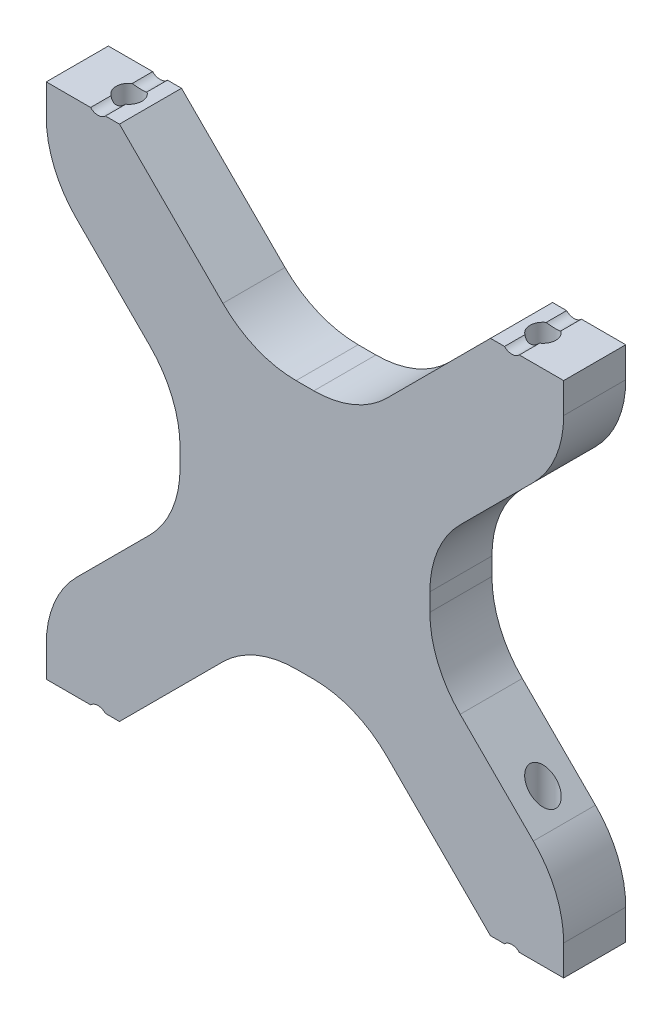
SolidWorks part; units mm, degrees
ref_plane "正面" through (0, 0, 0) normal (0, 0, 1) x (1, 0, 0)
ref_plane "平面" through (0, 0, 0) normal (0, 1, 0) x (1, 0, 0)
ref_plane "右側面" through (0, 0, 0) normal (1, 0, 0) x (0, 0, -1)
sketch "ｽｹｯﾁ1" plane through (0, 0, 0) normal (0, 0, 1) x (1, 0, 0)
  line L0 (-32.0711, 25) -> (-12.0711, 5)
  line L1 (-12.0711, -5) -> (-32.0711, -25)
  line L2 (-32.0711, -25) -> (-17.9289, -25)
  line L3 (-17.9289, -25) -> (-5, -12.0711)
  line L4 (5, -12.0711) -> (17.9289, -25)
  line L5 (17.9289, -25) -> (32.0711, -25)
  line L6 (32.0711, -25) -> (12.0711, -5)
  line L7 (12.0711, 5) -> (32.0711, 25)
  line L8 (32.0711, 25) -> (17.9289, 25)
  line L9 (17.9289, 25) -> (5, 12.0711)
  line L10 (-5, 12.0711) -> (-17.9289, 25)
  line L11 (-17.9289, 25) -> (-32.0711, 25)
  line L12 (-12.0711, 5) -> (-12.0711, -5)
  line L13 (-5, -12.0711) -> (5, -12.0711)
  line L14 (12.0711, -5) -> (12.0711, 5)
  line L15 (5, 12.0711) -> (-5, 12.0711)
  line L16 (12.0711, 5) -> (-12.0711, -5) construction
  line L17 (-12.0711, 5) -> (12.0711, -5) construction
  line L18 (-12.0711, 5) -> (12.0711, 5) construction
  line L19 (5, 12.0711) -> (-5, -12.0711) construction
  line L20 (-5, 12.0711) -> (5, -12.0711) construction
  point P1 (0, 0)
  point P11 (0, 0)
  dimension "D1" = 10
  dimension "D2" = 135
  dimension "D3" = 10
  dimension "D4" = 10
  dimension "D5" = 50
  dimension "D6" = 135
extrude "ﾎﾞｽ - 押し出し1" add sketch "ｽｹｯﾁ1" along normal blind 6
sketch "ｽｹｯﾁ2" plane through (0, 0, 6) normal (0, 0, 1) x (1, 0, 0)
  line L0 (0, 0) -> (0, 38.1314) construction
  line L1 (-17.9289, 25) -> (-32.0711, 25) construction
  line L2 (-20.7141, 25) -> (-19.2859, 25)
  line L3 (20.7141, 25) -> (19.2859, 25)
  arc A0 (-20.7141, 25) -> (-19.2859, 25) centre (-20, 25.7) ccw
  arc A1 (20.7141, 25) -> (19.2859, 25) centre (20, 25.7) cw
  dimension "D1" = 20
  dimension "D2" = 2
  dimension "D3" = 0.7
extrude "ｶｯﾄ - 押し出し1" cut sketch "ｽｹｯﾁ2" against normal through all
fillet "ﾌｨﾚｯﾄ1" radius 2 2 edges at (32.0711, 25, 3) (-32.0711, 25, 3)
ref_plane "平面1" through (0, 0, 0) normal (0, 1, 0) x (1, 0, 0)
mirror "ﾐﾗｰ3" about plane through (0, 0, 0) normal (0, 1, 0) of "ｶｯﾄ - 押し出し1", "ﾌｨﾚｯﾄ1"
sketch "ｽｹｯﾁ3" plane through (0, 25, 0) normal (0, 1, 0) x (1, 0, 0)
  line L0 (-29.2426, -3) -> (29.2426, -3) construction
  line L1 (-29.2426, 0) -> (-29.2426, -6) construction
  line L2 (29.2426, -6) -> (29.2426, 0) construction
  line L3 (-20, 0) -> (-20, -6) construction
  line L4 (-19.2859, 0) -> (-20.7141, 0) construction
  line L5 (-20.7141, -6) -> (-19.2859, -6) construction
  line L6 (20, 0) -> (20, -6) construction
  line L7 (20.7141, 0) -> (19.2859, 0) construction
  line L8 (19.2859, -6) -> (20.7141, -6) construction
  circle A0 centre (-20, -3) radius 1.25
  circle A1 centre (20, -3) radius 1.25
  dimension "D1" = 2.5
extrude "ｶｯﾄ - 押し出し2" cut sketch "ｽｹｯﾁ3" against normal through all
sketch "ｽｹｯﾁ4" plane through (0, 0, 6) normal (0, 0, 1) x (1, 0, 0)
  line L0 (27.2426, 25) -> (20.7141, 25) construction
  line L2 (-25, -25) -> (-25, 25)
  line L4 (25, -25) -> (25, 25)
  line L5 (-25, -25) -> (25, 25) construction
  line L6 (-25, 25) -> (25, -25) construction
  line L7 (-27.2426, -25) -> (-20.7141, -25) construction
  line L8 (29.2426, 25) -> (25, 25)
  line L9 (29.2426, 25) -> (29.2426, -25)
  line L10 (29.2426, -25) -> (25, -25)
  line L11 (-29.2426, 25) -> (-29.2426, -25)
  line L12 (29.2426, 25) -> (-29.2426, -25) construction
  line L13 (29.2426, -25) -> (-29.2426, 25) construction
  line L14 (-25, -25) -> (-29.2426, -25)
  line L15 (-25, 25) -> (-29.2426, 25)
  arc A0 (-28.6569, -21.5858) -> (-27.2426, -25) centre (-27.2426, -23) ccw construction
  point P0 (0, 0)
  point P8 (0, 0)
extrude "ｶｯﾄ - 押し出し3" cut sketch "ｽｹｯﾁ4" against normal through all
fillet "ﾌｨﾚｯﾄ2" radius 10 12 edges at (25, 17.9289, 3) (12.0711, 5, 3) (12.0711, -5, 3) (25, -17.9289, 3) (5, -12.0711, 3) (-5, -12.0711, 3) (-25, -17.9289, 3) (-12.0711, -5, 3) (-12.0711, 5, 3) (-25, 17.9289, 3) (5, 12.0711, 3) (-5, 12.0711, 3)
